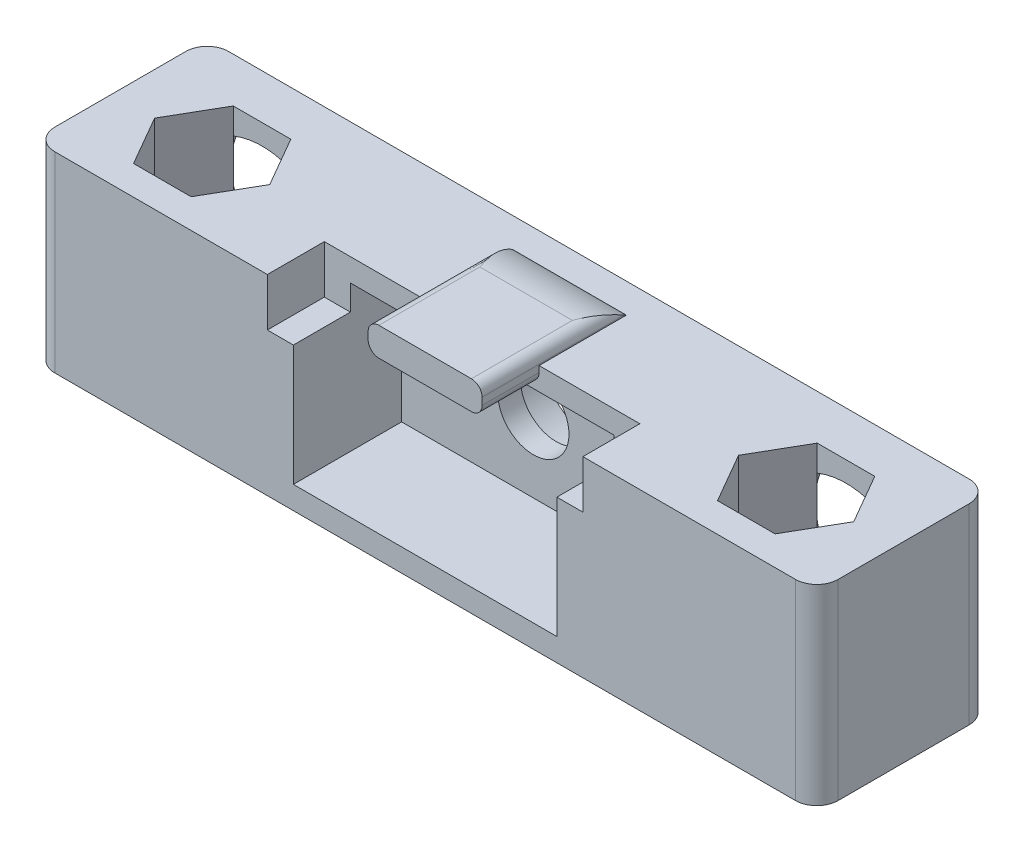
SolidWorks part; units mm, degrees
ref_plane "Front Plane" through (0, 0, 0) normal (0, 0, 1) x (1, 0, 0)
ref_plane "Top Plane" through (0, 0, 0) normal (0, 1, 0) x (1, 0, 0)
ref_plane "Right Plane" through (0, 0, 0) normal (1, 0, 0) x (0, 0, -1)
sketch "Sketch2" plane through (0, 0, 0) normal (0, 0, 1) x (1, 0, 0)
  line L1 (0, 0) -> (55, 0)
  line L2 (0, 0) -> (0, 13.45)
  line L3 (0, 13.45) -> (55, 13.45)
  line L4 (55, 0) -> (55, 13.45)
  dimension "D1" = 13.45
  dimension "D2" = 55
extrude "Boss-Extrude1" add sketch "Sketch2" along normal blind 12.2
sketch "Sketch3" plane through (0, 0, 12.2) normal (0, 0, 1) x (1, 0, 0)
  line L0 (0, 0) -> (55, 0) construction
  line L1 (18.25, 11.85) -> (36.75, 11.85)
  line L2 (18.25, 11.85) -> (18.25, 1.6)
  line L3 (18.25, 1.6) -> (36.75, 1.6)
  line L4 (36.75, 11.85) -> (36.75, 1.6)
  line L5 (27.5, 26.9) -> (27.5, 0) construction
  line L7 (27.5, 0) -> (27.5, -19.69) construction
  point P6 (27.5, 11.85)
  point P9 (27.5, 13.45)
  dimension "D1" = 1.6
  dimension "D2" = 18.5
  dimension "D3" = 11.85
extrude "Cut-Extrude1" cut sketch "Sketch3" against normal blind 7.6
sketch "Sketch5" plane through (0, 0, 12.2) normal (0, 0, 1) x (1, 0, 0)
  line L0 (27.5, 13.45) -> (27.5, -4.8209) construction
  line L1 (55, 13.45) -> (0, 13.45) construction
  line L3 (16.425, 13.45) -> (38.575, 13.45)
  line L4 (16.425, 13.45) -> (16.425, 11.85)
  line L5 (16.425, 11.85) -> (38.575, 11.85)
  line L6 (38.575, 13.45) -> (38.575, 11.85)
  point P1 (27.5, 13.45)
  dimension "D1" = 1.6
  dimension "D2" = 22.15
extrude "Cut-Extrude2" cut sketch "Sketch5" against normal blind 4
sketch "Sketch6" plane through (0, 0, 12.2) normal (0, 0, 1) x (1, 0, 0)
  line L0 (27.5, 0) -> (27.5, 20.3445) construction
  line L1 (0, 0) -> (55, 0) construction
  line L2 (36.75, 11.85) -> (18.25, 11.85) construction
  line L3 (23.5, 12.275) -> (31.5, 12.275)
  line L4 (23.5, 12.275) -> (23.5, 14.275)
  line L5 (23.5, 14.275) -> (31.5, 14.275)
  line L6 (31.5, 12.275) -> (31.5, 14.275)
  point P10 (27.5, 14.275)
  dimension "D1" = 0.425
  dimension "D2" = 8
  dimension "D3" = 2
extrude "Boss-Extrude2" add sketch "Sketch6" against normal blind 8.7
sketch "Sketch7" plane through (0, 0, 12.2) normal (0, 0, 1) x (1, 0, 0)
  line L0 (36.75, 1.6) -> (36.75, 11.85) construction
  line L1 (38.575, 13.45) -> (36.75, 13.45)
  line L2 (38.575, 13.45) -> (38.575, 10.075)
  line L3 (38.575, 10.075) -> (36.75, 10.075)
  line L4 (36.75, 13.45) -> (36.75, 10.075)
  line L5 (18.25, 11.85) -> (18.25, 1.6) construction
  line L6 (16.425, 13.45) -> (18.25, 13.45)
  line L7 (16.425, 13.45) -> (16.425, 10.075)
  line L8 (16.425, 10.075) -> (18.25, 10.075)
  line L9 (18.25, 13.45) -> (18.25, 10.075)
  dimension "D1" = 3.375
  dimension "D2" = 3.375
extrude "Cut-Extrude3" cut sketch "Sketch7" against normal up to surface (4 mm away) up to face at (27.5, 12.575, 8.2)
fillet "Fillet1" radius 0.75 2 edges at (31.5, 14.275, 7.85) (31.5, 12.275, 10.2)
fillet "Fillet3" radius 0.75 2 edges at (23.5, 12.275, 10.2) (23.5, 14.275, 7.85)
draft "Draft4" type of draft neutral plane draft angle 60 faces to draft 1 face at (27.5, 13.8018, 3.5) neutral plane through (23.5, 14.275, 3.5) neutral plane normal (0, 1, 0) parameters "D1"=60
fillet "Fillet5" radius 6 3 edges at (27.5, 14.275, 3.5) (31.2803, 14.0553, 3.1195) (23.7197, 14.0553, 3.1195)
sketch "Sketch8" plane through (0, 0, 4.6) normal (0, 0, 1) x (1, 0, 0)
  line L0 (18.25, 6.725) -> (36.75, 6.725) construction
  line L1 (18.25, 11.85) -> (18.25, 1.6) construction
  line L2 (27.5, 1.6) -> (27.5, 11.85) construction
  line L3 (18.25, 1.6) -> (36.75, 1.6) construction
  line L4 (36.75, 11.85) -> (18.25, 11.85) construction
  line L5 (36.75, 1.6) -> (36.75, 11.85) construction
  circle A0 centre (27.5, 6.725) radius 2.5
extrude "Cut-Extrude4" cut sketch "Sketch8" against normal through all
sketch "Sketch9" plane through (0, 0, 0) normal (0, 0, -1) x (-1, 0, 0)
  circle A0 centre (-27.5, 6.725) radius 4.25
extrude "Cut-Extrude5" cut sketch "Sketch9" against normal blind 3
sketch "Sketch10" plane through (0, 0, 0) normal (0, 0, -1) x (-1, 0, 0)
  line L0 (0, 6.725) -> (-55, 6.725) construction
  line L1 (0, 13.45) -> (0, 0) construction
  line L2 (-55, 0) -> (-55, 13.45) construction
  circle A0 centre (-48, 6.725) radius 5.3
  circle A1 centre (-7, 6.725) radius 5.3
  dimension "D1" = 7
  dimension "D2" = 7
extrude "Cut-Extrude6" cut sketch "Sketch10" against normal blind 3.15
sketch "Sketch11" plane through (0, 13.45, 0) normal (0, 1, 0) x (1, 0, 0)
  line L0 (0, -6.65) -> (55, -6.65) construction
  line L1 (9.0207, -3.15) -> (4.9793, -3.15)
  line L2 (4.9793, -3.15) -> (2.9585, -6.65)
  line L3 (2.9585, -6.65) -> (4.9793, -10.15)
  line L4 (4.9793, -10.15) -> (9.0207, -10.15)
  line L5 (9.0207, -10.15) -> (11.0415, -6.65)
  line L6 (11.0415, -6.65) -> (9.0207, -3.15)
  line L9 (27.5, -6.65) -> (27.5, -18.6651) construction
  line L10 (43.9585, -6.65) -> (45.9793, -3.15)
  line L11 (45.9793, -10.15) -> (43.9585, -6.65)
  line L12 (50.0207, -10.15) -> (45.9793, -10.15)
  line L13 (52.0415, -6.65) -> (50.0207, -10.15)
  line L14 (50.0207, -3.15) -> (52.0415, -6.65)
  line L15 (45.9793, -3.15) -> (50.0207, -3.15)
  line L17 (16.425, -12.2) -> (0, -12.2) construction
  circle A0 centre (7, -6.65) radius 3.5 construction
  circle A1 centre (48, -6.65) radius 3.5 construction
  dimension "D1" = 7
  dimension "D2" = 7
  dimension "D3" = 5.55
extrude "Cut-Extrude7" cut sketch "Sketch11" against normal blind 11
fillet "Fillet6" radius 1.5 4 edges at (0, 6.725, 12.2) (0, 6.725, 0) (55, 6.725, 12.2) (55, 6.725, 0)
